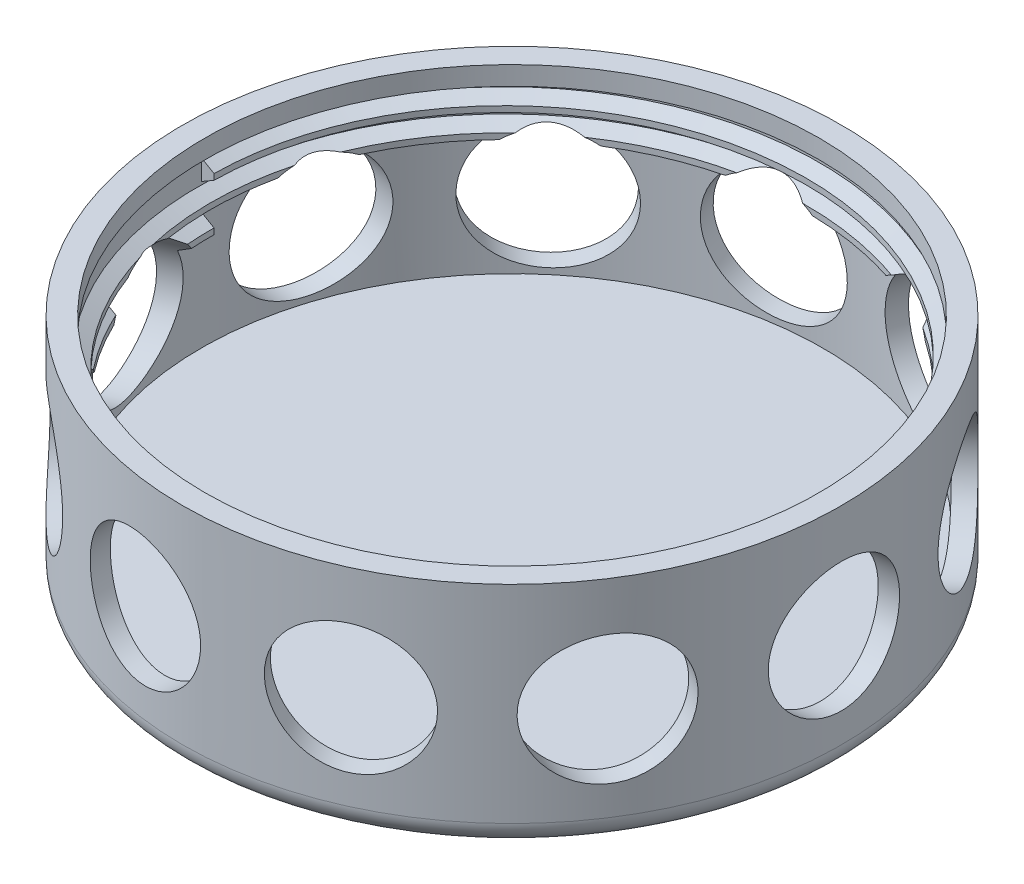
SolidWorks part; units mm, degrees
ref_plane "Front Plane" through (0, 0, 0) normal (0, 0, 1) x (1, 0, 0)
ref_plane "Top Plane" through (0, 0, 0) normal (0, 1, 0) x (1, 0, 0)
ref_plane "Right Plane" through (0, 0, 0) normal (1, 0, 0) x (0, 0, -1)
sketch "Szkic1" plane through (0, 0, 0) normal (0, 1, 0) x (1, 0, 0)
  circle A0 centre (0, 0) radius 14
  dimension "D1" = 28
extrude "Dodanie-wyciągnięcie2" add sketch "Szkic1" along normal blind 9 contours A0
sketch "Szkic5" plane through (0, 9, 0) normal (0, 1, 0) x (1, 0, 0)
  circle A0 centre (0, 0) radius 13.2
  dimension "D1" = 26.4
extrude "Wytnij-wyciągnięcie1" cut sketch "Szkic5" against normal blind 7
thread "Gwint1" pitch 1 method extrude profile "Profil gwintu2" start angle 0, offset 0, length 2, pitch 1, diameter 26.4
ref_plane "Płaszczyzna2" through (-13.2, 9, 0) normal (0, 0, 1) x (-1, 0, 0)
sketch "Profil gwintu2" plane through (-13.2, 9, 0) normal (0, 0, 1) x (-1, 0, 0)
  line L0 (0, 0) -> (0, 1) construction
  line L11 (0, 0) -> (0, 0.875)
  line L12 (0, 0.875) -> (-0.5413, 0.5625)
  line L13 (-0.5413, 0.5625) -> (-0.5413, 0.3125)
  line L15 (-0.5413, 0.3125) -> (0, 0)
  line L17 (-0.5413, 0.4375) -> (0, 0.4375) construction
  point P2 (0, 0)
  dimension "Pitch" = 1
  dimension "Profile_Angle" = 60
  dimension "Profile_Land" = 0.25
  dimension "Profile_Height" = 0.5413
ref_plane "Płaszczyzna3" through (0, 9, 0) normal (0, 1, 0) x (1, 0, 0)
sketch "Szkic22" plane through (0, 9, 0) normal (0, 1, 0) x (1, 0, 0)
  circle A0 centre (0, 0) radius 13.05
  circle A1 centre (0, 0) radius 14
  dimension "D1" = 28
extrude "Dodanie-wyciągnięcie3" add sketch "Szkic22" along normal blind 0.8
ref_plane "Płaszczyzna4" through (0, 0, 16) normal (0, 0, 1) x (1, 0, 0)
sketch "Szkic23" plane through (0, 0, 16) normal (0, 0, 1) x (1, 0, 0)
  line L0 (14, 0) -> (14, 9.8) construction
  circle A0 centre (-2, 5) radius 2.75
  dimension "D1" = 5.5
  dimension "D2" = 5
  dimension "D3" = 16
extrude "Wytnij-wyciągnięcie2" cut sketch "Szkic23" against normal blind 5
ref_axis "Oś1" through (0, 0, 0) along (0, -1, 0)
pattern_circular "Szyk kołowy1" count 11 over 360 about axis through (0, 0, 0) along (0, -1, 0) of "Wytnij-wyciągnięcie2"
fillet "Zaokrąglenie1" radius 1 1 edges at (0, 0, 14)
